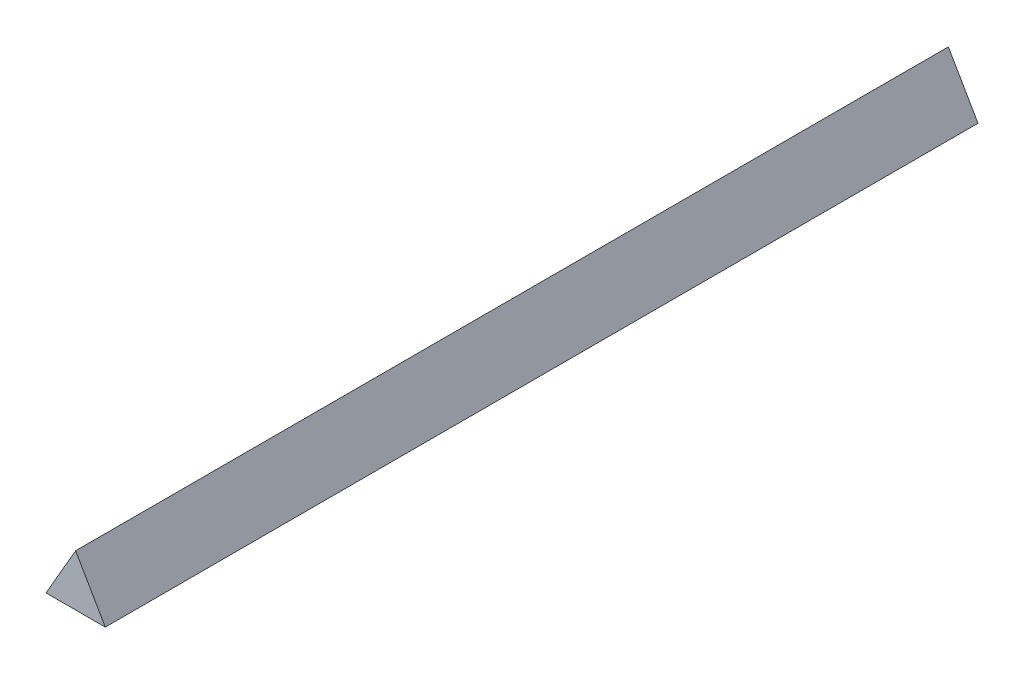
SolidWorks part; units mm, degrees
ref_plane "Спереди" through (0, 0, 0) normal (0, 0, 1) x (1, 0, 0)
ref_plane "Сверху" through (0, 0, 0) normal (0, 1, 0) x (1, 0, 0)
ref_plane "Справа" through (0, 0, 0) normal (1, 0, 0) x (0, 0, -1)
sketch "Эскиз1" plane through (0, 0, 0) normal (0, 0, 1) x (1, 0, 0)
  line L0 (-1.1547, -0.6667) -> (0, 1.3333)
  line L1 (0, 1.3333) -> (1.1547, -0.6667)
  line L2 (1.1547, -0.6667) -> (-1.1547, -0.6667)
  circle A0 centre (0, 0) radius 1.3333 construction
  point P5 (-0.0521, 1.3296)
  dimension "D1" = 2
extrude "Бобышка-Вытянуть1" add sketch "Эскиз1" along normal blind 34
